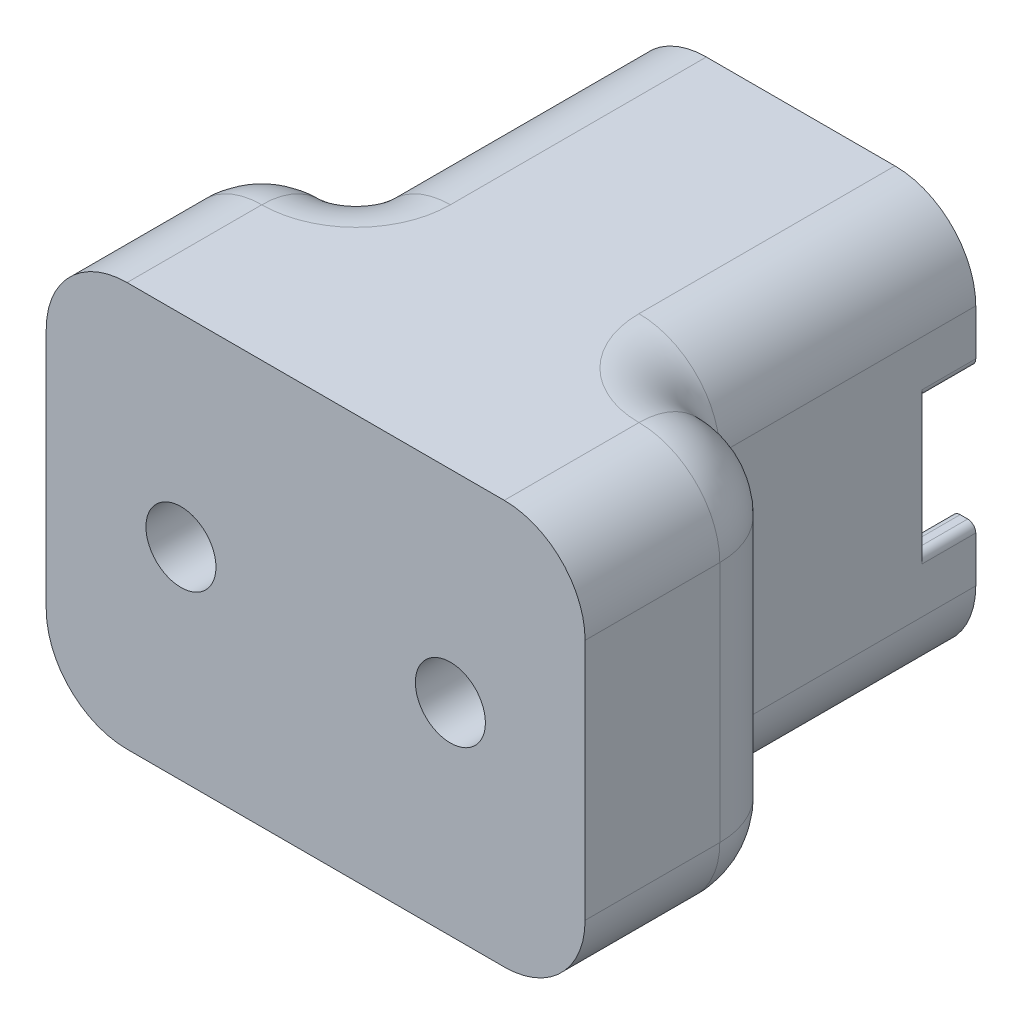
SolidWorks part; units mm, degrees
material "ﾎﾟﾘｴﾁﾚﾝｲﾐﾝ(PEI)"
ref_plane "正面" through (0, 0, 0) normal (0, 0, 1) x (1, 0, 0)
ref_plane "平面" through (0, 0, 0) normal (0, 1, 0) x (1, 0, 0)
ref_plane "右側面" through (0, 0, 0) normal (1, 0, 0) x (0, 0, -1)
sketch "ｽｹｯﾁ1" plane through (0, 0, 0) normal (0, 0, 1) x (1, 0, 0)
  line L1 (6.5, 7.5) -> (-6.5, 7.5)
  line L2 (6.5, 7.5) -> (6.5, -7.5)
  line L3 (6.5, -7.5) -> (-6.5, -7.5)
  line L4 (-6.5, 7.5) -> (-6.5, -7.5)
  line L5 (6.5, 7.5) -> (-6.5, -7.5) construction
  line L6 (6.5, -7.5) -> (-6.5, 7.5) construction
  point P0 (0, 0)
  dimension "D1" = 13
  dimension "D2" = 15
extrude "ﾎﾞｽ - 押し出し1" add sketch "ｽｹｯﾁ1" along normal blind 10
sketch "ｽｹｯﾁ2" plane through (0, 0, 10) normal (0, 0, 1) x (1, 0, 0)
  line L1 (10, 7.5) -> (-10, 7.5)
  line L2 (10, 7.5) -> (10, -7.5)
  line L3 (10, -7.5) -> (-10, -7.5)
  line L4 (-10, 7.5) -> (-10, -7.5)
  line L5 (10, 7.5) -> (-10, -7.5) construction
  line L6 (10, -7.5) -> (-10, 7.5) construction
  point P0 (0, 0)
  dimension "D1" = 20
  dimension "D2" = 15
extrude "ﾎﾞｽ - 押し出し2" add sketch "ｽｹｯﾁ2" along normal blind 8
sketch "ｽｹｯﾁ6" plane through (0, 0, 0) normal (0, 0, -1) x (-1, 0, 0)
  line L0 (-6.5, -7.5) -> (-6.5, 7.5) construction
  line L1 (6.5, -2.5) -> (-6.5, -2.5)
  line L2 (6.5, -2.5) -> (6.5, 2.5)
  line L3 (6.5, 2.5) -> (-6.5, 2.5)
  line L4 (-6.5, -2.5) -> (-6.5, 2.5)
  line L5 (6.5, -2.5) -> (-6.5, 2.5) construction
  line L6 (6.5, 2.5) -> (-6.5, -2.5) construction
  circle A0 centre (0, 0) radius 6.25
  line M2 (6.5, -7.5) -> (6.5, 7.5)
  dimension "D1" = 12.5
  dimension "D2" = 5
extrude "ｶｯﾄ - 押し出し3" cut sketch "ｽｹｯﾁ6" against normal blind 2 contours L3 A0 | L3 A0 L1 | L1 A0 | A0 L1 L3 M2 | L4 L3 L2 L1 region at (-6.2612, 0, 0) region at (0, -4.0468, 0) region at (0, 0, 0) region at (0, 4.0468, 0)
sketch "ｽｹｯﾁ8" plane through (0, 0, 18) normal (0, 0, 1) x (1, 0, 0)
  line L0 (-10, 0) -> (10, 0) construction
  line L1 (-10, 7.5) -> (-10, -7.5) construction
  line L2 (10, -7.5) -> (10, 7.5) construction
  circle A0 centre (-5, 0) radius 1.3
  circle A1 centre (5, 0) radius 1.3
  dimension "D1" = 2.6
  dimension "D2" = 5
  dimension "D3" = 2.6
  dimension "D4" = 5
extrude "ｶｯﾄ - 押し出し5" cut sketch "ｽｹｯﾁ8" against normal blind 10
fillet "ﾌｨﾚｯﾄ7" radius 0.5 2 edges at (-6.5, 0, 10) (6.5, 0, 10)
fillet "ﾌｨﾚｯﾄ8" radius 3 2 edges at (10, 0, 10) (-10, 0, 10)
fillet "ﾌｨﾚｯﾄ9" radius 3 16 edges at (-6.5, 7.5, 4.75) (-6.6464, 7.5, 9.8536) (-9.1213, 7.5, 10.8787) (6.5, 7.5, 4.75) (6.6464, 7.5, 9.8536) (9.1213, 7.5, 10.8787) (6.5, -7.5, 4.75) (6.6464, -7.5, 9.8536) (9.1213, -7.5, 10.8787) (-6.5, -7.5, 4.75) (-6.6464, -7.5, 9.8536) (-9.1213, -7.5, 10.8787) (-10, 7.5, 15.5) (10, 7.5, 15.5) (10, -7.5, 15.5) (-10, -7.5, 15.5)
fillet "ﾌｨﾚｯﾄ10" radius 0.3 8 edges at (6.5, -2.5, 1) (5.7282, -2.5, 1) (-5.7282, -2.5, 1) (-6.5, -2.5, 1) (-6.5, 2.5, 1) (-5.7282, 2.5, 1) (5.7282, 2.5, 1) (6.5, 2.5, 1)
